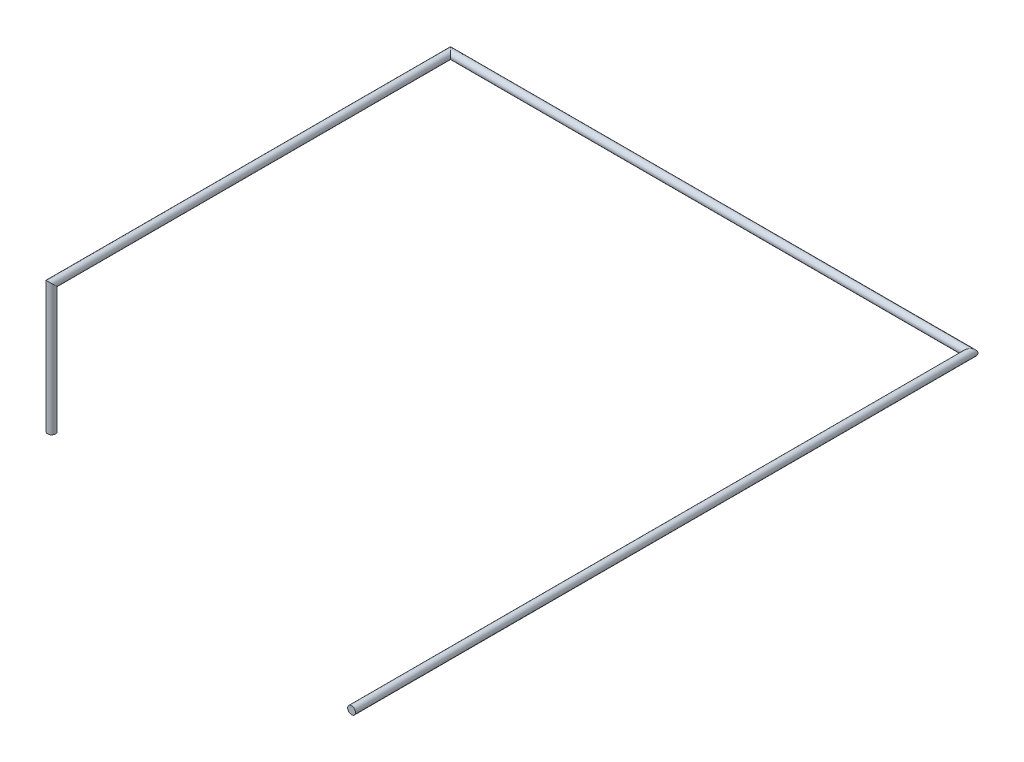
SolidWorks part; units mm, degrees
ref_plane "Alzado" through (0, 0, 0) normal (0, 0, 1) x (1, 0, 0)
ref_plane "Planta" through (0, 0, 0) normal (0, 1, 0) x (1, 0, 0)
ref_plane "Vista lateral" through (0, 0, 0) normal (1, 0, 0) x (0, 0, -1)
sketch "Croquis1" plane through (0, 0, 0) normal (0, 1, 0) x (1, 0, 0)
  circle A0 centre (0, 0) radius 12.7
  dimension "D1" = 25.4
extrude "Saliente-Extruir1" add sketch "Croquis1" along normal blind 10
sketch3d "Croquis3D1"
  line L0 (0, 10, 0) -> (0, 415, 0)
  line L1 (0, 10, 0) -> (0, 0, 0) construction
  line L2 (0, 415, 0) -> (0, 415, -1290)
  line L3 (0, 415, -1290) -> (1680, 415, -1290)
  line L4 (1680, 415, -1290) -> (1680, 415, 710)
  dimension "D1" = 405
  dimension "D2" = 1290
  dimension "D3" = 1680
  dimension "D4" = 2000
sketch "Croquis2" plane through (0, 10, 0) normal (0, 1, 0) x (1, 0, 0)
  circle A0 centre (0, 0) radius 12.7
  dimension "D1" = 25.4
sweep "Barrer1" add profiles "Croquis2" path "Croquis3D1"
sketch "Croquis3" plane through (0, 0, 0) normal (0, -1, 0) x (1, 0, 0)
  line L1 (-0.8166, 12.4574) -> (0.8166, 12.4574)
  line L2 (-0.8166, 12.4574) -> (-0.8166, 12.9426)
  line L3 (-0.8166, 12.9426) -> (0.8166, 12.9426)
  line L4 (0.8166, 12.4574) -> (0.8166, 12.9426)
  line L5 (-0.8166, 12.4574) -> (0.8166, 12.9426) construction
  line L6 (-0.8166, 12.9426) -> (0.8166, 12.4574) construction
  circle A0 centre (0, 0) radius 12.7 construction
  point P0 (0, 12.7)
extrude "Saliente-Extruir2" add sketch "Croquis3" against normal blind 1
